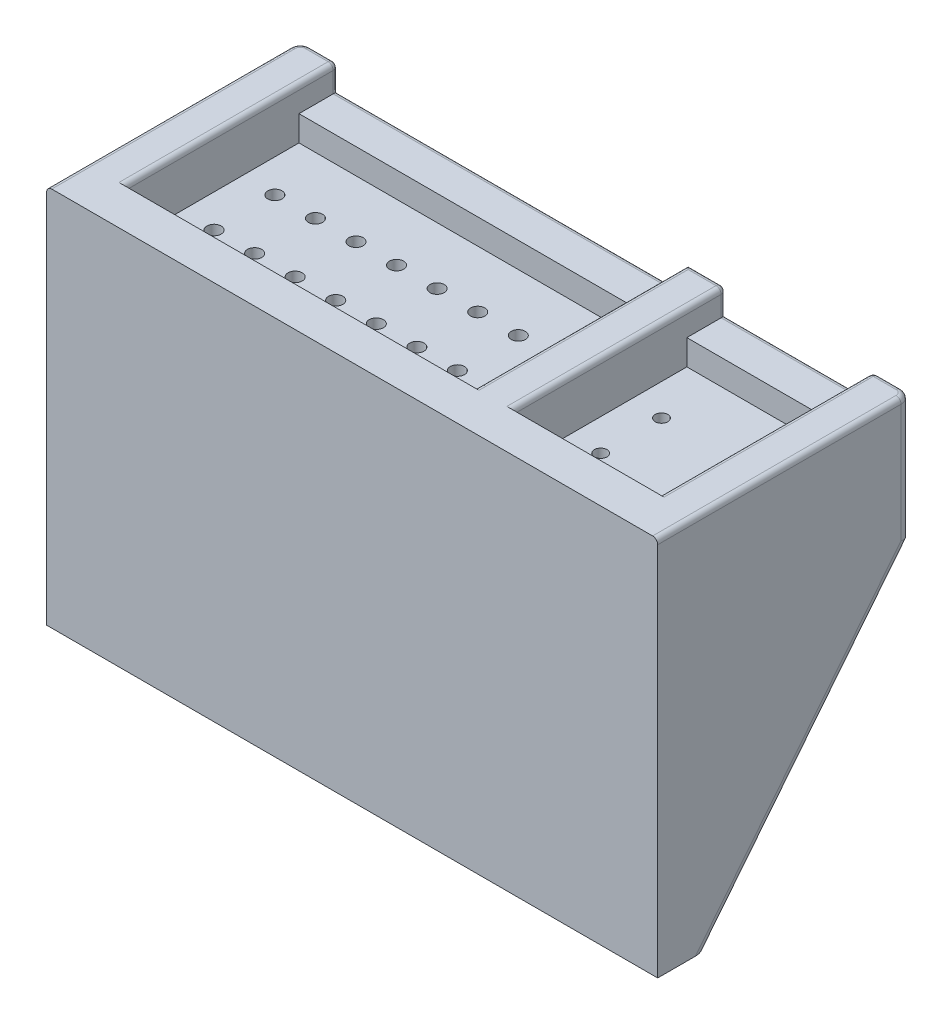
SolidWorks part; units mm, degrees
ref_plane "Front Plane" through (0, 0, 0) normal (0, 0, 1) x (1, 0, 0)
ref_plane "Top Plane" through (0, 0, 0) normal (0, 1, 0) x (1, 0, 0)
ref_plane "Right Plane" through (0, 0, 0) normal (1, 0, 0) x (0, 0, -1)
sketch "Sketch1" plane through (0, 0, 0) normal (0, 1, 0) x (1, 0, 0)
  line L1 (-60.25, -25) -> (60.25, -25)
  line L2 (-60.25, -25) -> (-60.25, 25)
  line L3 (-60.25, 25) -> (60.25, 25)
  line L4 (60.25, -25) -> (60.25, 25)
  line L5 (-60.25, -25) -> (60.25, 25) construction
  line L6 (-60.25, 25) -> (60.25, -25) construction
  point P0 (0, 0)
  dimension "D1" = 120.5
  dimension "D2" = 50
extrude "Boss-Extrude1" add sketch "Sketch1" along normal blind 25
sketch "Sketch2" plane through (0, 25, 0) normal (0, 1, 0) x (1, 0, 0)
  line L1 (23.75, -17.25) -> (52.75, -17.25)
  line L2 (23.75, -17.25) -> (23.75, 17.25)
  line L3 (23.75, 17.25) -> (52.75, 17.25)
  line L4 (52.75, -17.25) -> (52.75, 17.25)
  line L5 (23.75, -17.25) -> (52.75, 17.25) construction
  line L6 (23.75, 17.25) -> (52.75, -17.25) construction
  line L7 (60.25, -25) -> (60.25, 25) construction
  point P0 (38.25, 0)
  point P5 (0, 0)
  dimension "D1" = 34.5
  dimension "D2" = 29
  dimension "D3" = 7.5
extrude "Cut-Extrude1" cut sketch "Sketch2" against normal blind 10
sketch "Sketch3" plane through (0, 25, 0) normal (0, 1, 0) x (1, 0, 0)
  line L0 (23.75, 17.25) -> (23.75, -17.25) construction
  line L1 (-52.75, -17.25) -> (16.25, -17.25)
  line L2 (-52.75, -17.25) -> (-52.75, 17.25)
  line L3 (-52.75, 17.25) -> (16.25, 17.25)
  line L4 (16.25, -17.25) -> (16.25, 17.25)
  line L5 (-52.75, -17.25) -> (16.25, 17.25) construction
  line L6 (-52.75, 17.25) -> (16.25, -17.25) construction
  point P0 (-18.25, 0)
  point P7 (0, 0)
  dimension "D1" = 7.5
  dimension "D2" = 69
  dimension "D3" = 34.5
extrude "Cut-Extrude2" cut sketch "Sketch3" against normal blind 10
sketch "Sketch5" plane through (0, 15, 0) normal (0, 1, 0) x (1, 0, 0)
  line L0 (-48.7346, 0) -> (32.4983, 0) construction
  line L2 (-46.25, 6) -> (-38.25, 6) construction
  line L4 (-52.75, 17.25) -> (16.25, -17.25) construction
  line L5 (16.25, 17.25) -> (-52.75, -17.25) construction
  line L6 (-18.25, 0) -> (-41.795, 0) construction
  line L7 (-18.25, 0) -> (-18.25, 11.1048) construction
  line L8 (-52.75, 17.25) -> (-52.75, -17.25) construction
  circle A19 centre (-46.25, 6) radius 1.4
  circle A20 centre (-38.25, 6) radius 1.4
  circle A21 centre (-30.25, 6) radius 1.4
  circle A22 centre (-22.25, 6) radius 1.4
  circle A23 centre (-14.25, 6) radius 1.4
  circle A24 centre (-6.25, 6) radius 1.4
  circle A25 centre (1.75, 6) radius 1.4
  circle A26 centre (9.75, 6) radius 1.4
  circle A27 centre (-38.25, -6) radius 1.4
  circle A28 centre (-30.25, -6) radius 1.4
  circle A29 centre (-22.25, -6) radius 1.4
  circle A30 centre (-14.25, -6) radius 1.4
  circle A31 centre (-6.25, -6) radius 1.4
  circle A32 centre (1.75, -6) radius 1.4
  circle A33 centre (9.75, -6) radius 1.4
  circle A34 centre (-46.25, -6) radius 1.4
  dimension "D6" = 8
  dimension "D7" = 2.8
  dimension "D4" = 28
  dimension "D1" = 6
  dimension "D2" = 0
  dimension "D3" = 2
extrude "Cut-Extrude4" cut sketch "Sketch5" against normal through all
sketch "Sketch6" plane through (0, 15, 0) normal (0, 1, 0) x (1, 0, 0)
  line L0 (30, 6) -> (46, 6) construction
  line L1 (46, 6) -> (46, -6) construction
  line L2 (46, -6) -> (30, -6) construction
  line L3 (30, -6) -> (30, 6) construction
  line L6 (23.75, 17.25) -> (52.75, -17.25) construction
  line L7 (52.75, -17.25) -> (52.75, 17.25) construction
  line L8 (52.75, -17.25) -> (52.75, 17.25) construction
  line L9 (52.75, 17.25) -> (23.75, -17.25) construction
  circle A0 centre (30, 6) radius 1.25
  circle A1 centre (46, 6) radius 1.25
  point P17 (38.25, 0)
  dimension "D5" = 2.5
  dimension "D6" = 2.5
  dimension "D1" = 6
  dimension "D3" = 16
  dimension "D4" = 12
extrude "Cut-Extrude5" cut sketch "Sketch6" against normal through all
mirror "Mirror3" about plane through (0, 0, 0) normal (0, 0, 1) of "Cut-Extrude5"
sketch "Sketch8" plane through (0, 25, 0) normal (0, 1, 0) x (1, 0, 0)
  line L0 (-52.75, 17.25) -> (16.25, 17.25)
  line L1 (16.25, 17.25) -> (16.25, 25)
  line L2 (60.25, 25) -> (-60.25, 25) construction
  line L3 (16.25, 25) -> (-52.75, 25)
  line L4 (-52.75, 25) -> (-52.75, 17.25)
  line L5 (23.75, 17.25) -> (52.75, 17.25)
  line L6 (52.75, 17.25) -> (52.75, 25)
  line L7 (52.75, 25) -> (23.75, 25)
  line L8 (23.75, 25) -> (23.75, 17.25)
extrude "Cut-Extrude7" cut sketch "Sketch8" against normal blind 5
fillet "Fillet1" radius 1 14 edges at (52.75, 22.5, -25) (-18.25, 20, -25) (38.25, 20, -25) (-52.75, 22.5, -25) (23.75, 22.5, -25) (16.25, 25, -3.875) (20, 25, -25) (23.75, 25, -3.875) (52.75, 25, -3.875) (56.5, 25, -25) (60.25, 25, 0) (-60.25, 25, 0) (-56.5, 25, -25) (-52.75, 25, -3.875)
sketch "Sketch9" plane through (0, 0, 0) normal (0, -1, 0) x (1, 0, 0)
  line L0 (-60.25, -25) -> (-60.25, 25) construction
  line L1 (60.25, 25) -> (-60.25, 25)
  line L2 (60.25, 25) -> (60.25, 15)
  line L3 (60.25, 15) -> (-60.25, 15)
  line L4 (-60.25, 25) -> (-60.25, 15)
  dimension "D1" = 10
extrude "Boss-Extrude2" add sketch "Sketch9" along normal blind 50
sketch "Sketch10" plane through (-60.25, 0, 0) normal (-1, 0, 0) x (0, 0, 1)
  line L0 (-25, 0) -> (15, -50)
  line L1 (15, -50) -> (15, 0)
  line L2 (15, 0) -> (-25, 0)
extrude "Boss-Extrude3" add sketch "Sketch10" against normal blind 10
mirror "Mirror4" about plane through (0, 0, 0) normal (1, 0, 0) of "Boss-Extrude3"
fillet "Fillet3" radius 2 8 edges at (-59.9571, 24.7071, -24.7071) (59.9571, 24.7071, -24.7071) (60.25, 12, -25) (-60.25, 12, -25) (-60.25, -25, -5) (60.25, -25, -5) (-50.25, -25, -5) (50.25, -25, -5)
